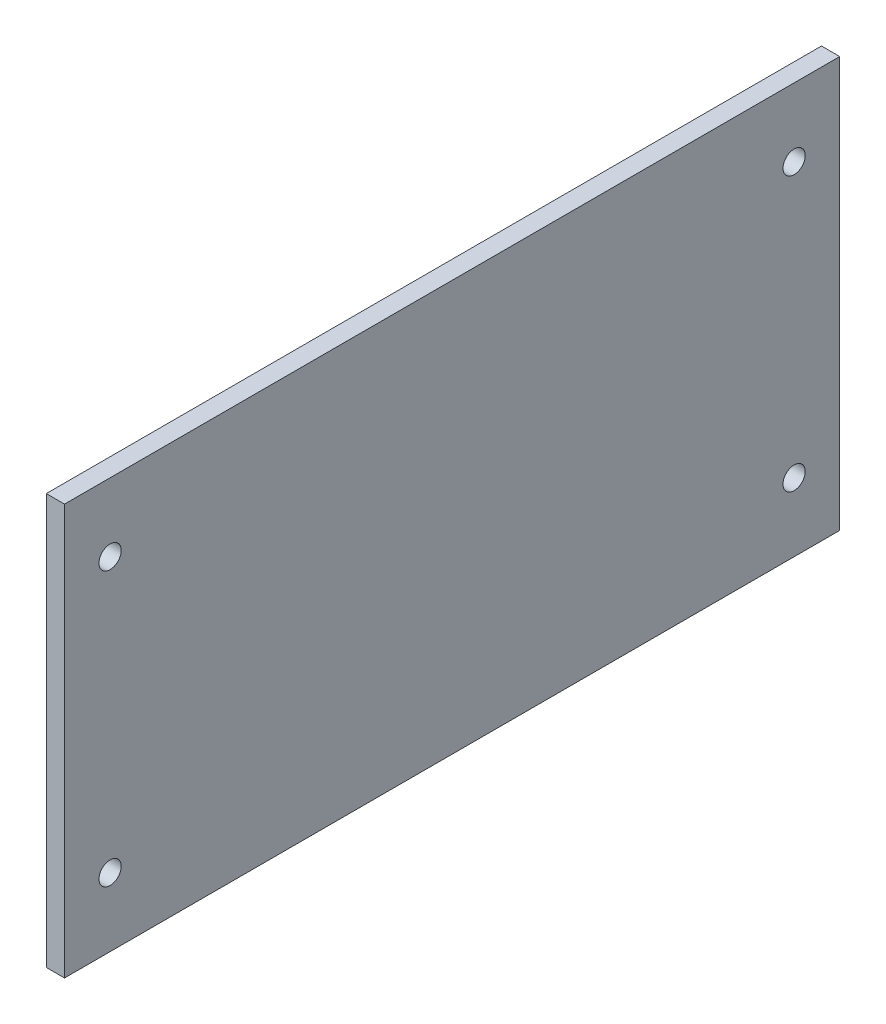
SolidWorks part; units mm, degrees
material "PCB (FR-4)"
ref_plane "Front Plane" through (0, 0, 0) normal (0, 0, 1) x (1, 0, 0)
ref_plane "Top Plane" through (0, 0, 0) normal (0, 1, 0) x (1, 0, 0)
ref_plane "Right Plane" through (0, 0, 0) normal (1, 0, 0) x (0, 0, -1)
sketch "Sketch1" plane through (0, 0, 0) normal (1, 0, 0) x (0, 0, -1)
  line L1 (-42.5, -22.5) -> (42.5, -22.5)
  line L2 (-42.5, -22.5) -> (-42.5, 22.5)
  line L3 (-42.5, 22.5) -> (42.5, 22.5)
  line L4 (42.5, -22.5) -> (42.5, 22.5)
  line L5 (-42.5, -22.5) -> (42.5, 22.5) construction
  line L6 (-42.5, 22.5) -> (42.5, -22.5) construction
  point P0 (0, 0)
  dimension "D1" = 45
  dimension "D2" = 85
extrude "Boss-Extrude1" add sketch "Sketch1" along normal blind 2
sketch "Sketch2" plane through (2, 0, 0) normal (1, 0, 0) x (0, 0, -1)
  line L0 (0, 0) -> (-37.5, 0) construction
  line L1 (-37.5, 0) -> (-37.5, -15) construction
  line L2 (0, 0) -> (37.5, 0) construction
  line L3 (37.5, 0) -> (37.5, 15) construction
  line L4 (37.5, 0) -> (37.5, -15) construction
  line L5 (-37.5, 0) -> (-37.5, 15) construction
  circle A0 centre (-37.5, -15) radius 1.0922
  circle A1 centre (37.5, -15) radius 1.0922
  circle A2 centre (37.5, 15) radius 1.0922
  circle A3 centre (-37.5, 15) radius 1.0922
  dimension "D3" = 2.1844
  dimension "D1" = 37.5
  dimension "D2" = 15
  dimension "D5" = 2
  dimension "D4" = 2
hole_wizard "#2 Clearance Hole1" positions "Sketch5" profile "Sketch6" hole size "#2" standard "ANSI Inch"
sketch "Sketch5" plane through (2, 0, 0) normal (1, 0, 0) x (0, 0, -1)
  point P0 (-37.5, 15)
  point P3 (-37.5, -15)
  point P6 (37.5, -15)
  point P9 (37.5, 15)
sketch "Sketch6" plane through (2, 15, 37.5) normal (0, 1, 0) x (0, 0, -1)
  line L0 (0, 0) -> (0, 3.7326)
  line L1 (0, 3.7326) -> (1.2192, 3)
  line L2 (1.2192, 3) -> (1.2192, 0)
  line L5 (1.2192, 0) -> (0, 0)
  line L10 (0, 3.7326) -> (-1.2192, 3) construction
  line L11 (0, -6.35) -> (0, 107.95) construction
  dimension "Hole Dia." = 2.4384
  dimension "Hole Depth" = 3
  dimension "Drill Angle" = 118
